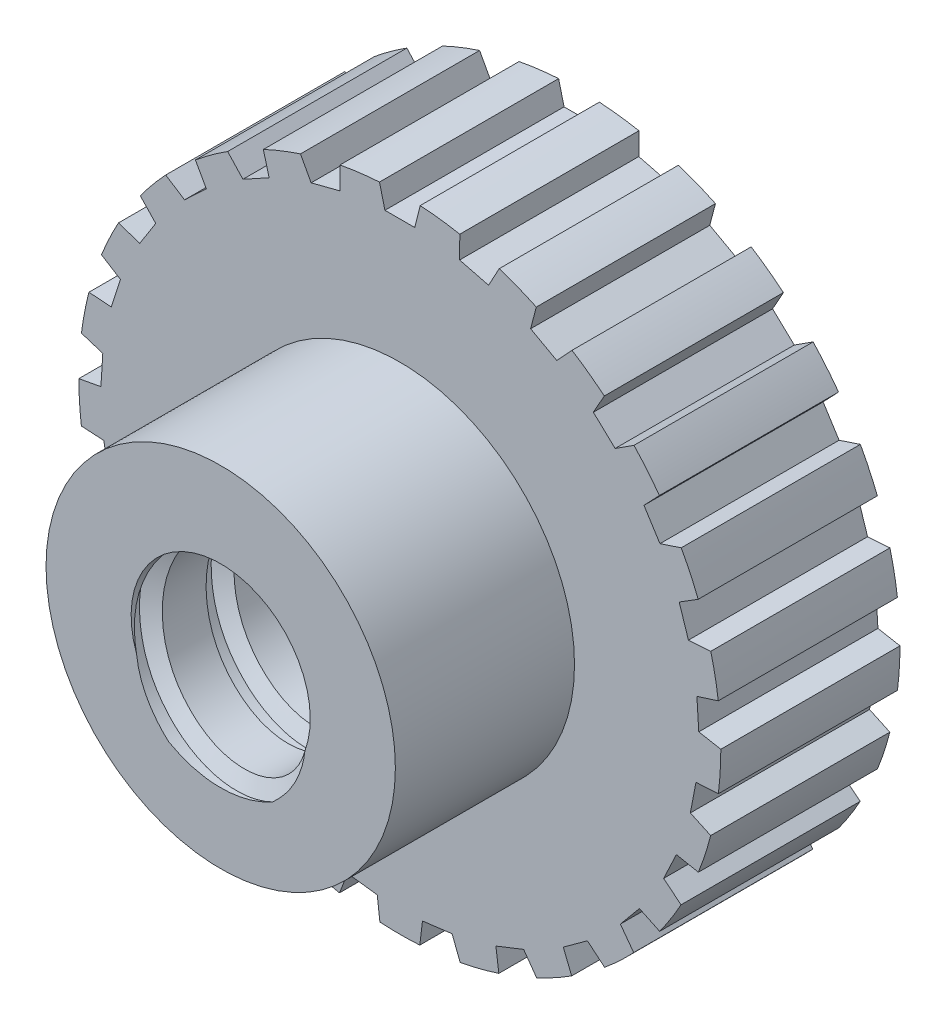
SolidWorks part; units mm, degrees
ref_plane "Front Plane" through (0, 0, 0) normal (0, 0, 1) x (1, 0, 0)
ref_plane "Top Plane" through (0, 0, 0) normal (0, 1, 0) x (1, 0, 0)
ref_plane "Right Plane" through (0, 0, 0) normal (1, 0, 0) x (0, 0, -1)
sketch "Sketch1" plane through (0, 0, 0) normal (0, 0, 1) x (1, 0, 0)
  circle A0 centre (0, 0) radius 5.375
  dimension "D1" = 10.75
extrude "Boss-Extrude2" add sketch "Sketch1" along normal blind 3
sketch "Sketch3" plane through (0, 0, 3) normal (0, 0, 1) x (1, 0, 0)
  circle A0 centre (0, 0) radius 2.925
  dimension "D1" = 5.85
extrude "Boss-Extrude3" add sketch "Sketch3" along normal blind 3
sketch "Sketch4" plane through (0, 0, 6) normal (0, 0, 1) x (1, 0, 0)
  circle A0 centre (0, 0) radius 1.5
  dimension "D1" = 3
extrude "Cut-Extrude1" cut sketch "Sketch4" against normal blind 8
sketch "Sketch5" plane through (0, 0, 3) normal (0, 0, 1) x (1, 0, 0)
  line L0 (0, 0) -> (0, 6.6562) construction
  line L1 (-0.5, 6) -> (0.5, 6)
  line L2 (0.5, 6) -> (0.25, 5)
  line L3 (0.25, 5) -> (-0.25, 5)
  line L4 (-0.25, 5) -> (-0.5, 6)
  line L5 (1.9764, 5.6872) -> (1.4856, 4.7807)
  line L6 (1.0078, 5.9358) -> (1.9764, 5.6872)
  line L7 (1.0013, 4.9051) -> (1.0078, 5.9358)
  line L8 (1.4856, 4.7807) -> (1.0013, 4.9051)
  line L9 (3.3287, 5.017) -> (2.6278, 4.2611)
  line L10 (2.4524, 5.4987) -> (3.3287, 5.017)
  line L11 (2.1897, 4.502) -> (2.4524, 5.4987)
  line L12 (2.6278, 4.2611) -> (2.1897, 4.502)
  line L13 (4.4718, 4.0315) -> (3.605, 3.4737)
  line L14 (3.7428, 4.7161) -> (4.4718, 4.0315)
  line L15 (3.2405, 3.816) -> (3.7428, 4.7161)
  line L16 (3.605, 3.4737) -> (3.2405, 3.816)
  line L17 (5.3339, 2.7928) -> (4.3556, 2.4681)
  line L18 (4.7981, 3.6371) -> (5.3339, 2.7928)
  line L19 (4.0877, 2.8902) -> (4.7981, 3.6371)
  line L20 (4.3556, 2.4681) -> (4.0877, 2.8902)
  line L21 (5.8608, 1.3786) -> (4.8325, 1.3073)
  line L22 (5.5518, 2.3296) -> (5.8608, 1.3786)
  line L23 (4.678, 1.7828) -> (5.5518, 2.3296)
  line L24 (4.8325, 1.3073) -> (4.678, 1.7828)
  line L25 (6.0196, -0.1223) -> (5.0058, 0.0644)
  line L26 (5.9568, 0.8758) -> (6.0196, -0.1223)
  line L27 (4.9744, 0.5635) -> (5.9568, 0.8758)
  line L28 (5.0058, 0.0644) -> (4.9744, 0.5635)
  line L29 (5.8, -1.6154) -> (4.8646, -1.1825)
  line L30 (5.9874, -0.6331) -> (5.8, -1.6154)
  line L31 (4.9583, -0.6913) -> (5.9874, -0.6331)
  line L32 (4.8646, -1.1825) -> (4.9583, -0.6913)
  line L33 (5.2161, -3.0071) -> (4.4177, -2.3551)
  line L34 (5.6419, -2.1023) -> (5.2161, -3.0071)
  line L35 (4.6306, -1.9027) -> (5.6419, -2.1023)
  line L36 (4.4177, -2.3551) -> (4.6306, -1.9027)
  line L37 (4.3044, -4.2098) -> (3.6932, -3.3797)
  line L38 (4.9418, -3.4393) -> (4.3044, -4.2098)
  line L39 (4.0119, -2.9945) -> (4.9418, -3.4393)
  line L40 (3.6932, -3.3797) -> (4.0119, -2.9945)
  line L41 (3.1222, -5.148) -> (2.7367, -4.192)
  line L42 (3.9312, -4.5602) -> (3.1222, -5.148)
  line L43 (3.1412, -3.8981) -> (3.9312, -4.5602)
  line L44 (2.7367, -4.192) -> (3.1412, -3.8981)
  line L45 (1.7439, -5.7627) -> (1.6082, -4.7409)
  line L46 (2.6736, -5.3946) -> (1.7439, -5.7627)
  line L47 (2.0731, -4.5569) -> (2.6736, -5.3946)
  line L48 (1.6082, -4.7409) -> (2.0731, -4.5569)
  line L49 (0.2559, -6.0154) -> (0.3786, -4.9919)
  line L50 (1.2481, -5.89) -> (0.2559, -6.0154)
  line L51 (0.8747, -4.9292) -> (1.2481, -5.89)
  line L52 (0.3786, -4.9919) -> (0.8747, -4.9292)
  line L53 (-1.2481, -5.89) -> (-0.8747, -4.9292)
  line L54 (-0.2559, -6.0154) -> (-1.2481, -5.89)
  line L55 (-0.3786, -4.9919) -> (-0.2559, -6.0154)
  line L56 (-0.8747, -4.9292) -> (-0.3786, -4.9919)
  line L57 (-2.6736, -5.3946) -> (-2.0731, -4.5569)
  line L58 (-1.7439, -5.7627) -> (-2.6736, -5.3946)
  line L59 (-1.6082, -4.7409) -> (-1.7439, -5.7627)
  line L60 (-2.0731, -4.5569) -> (-1.6082, -4.7409)
  line L61 (-3.9312, -4.5602) -> (-3.1412, -3.8981)
  line L62 (-3.1222, -5.148) -> (-3.9312, -4.5602)
  line L63 (-2.7367, -4.192) -> (-3.1222, -5.148)
  line L64 (-3.1412, -3.8981) -> (-2.7367, -4.192)
  line L65 (-4.9418, -3.4393) -> (-4.0119, -2.9945)
  line L66 (-4.3044, -4.2098) -> (-4.9418, -3.4393)
  line L67 (-3.6932, -3.3797) -> (-4.3044, -4.2098)
  line L68 (-4.0119, -2.9945) -> (-3.6932, -3.3797)
  line L69 (-5.6419, -2.1023) -> (-4.6306, -1.9027)
  line L70 (-5.2161, -3.0071) -> (-5.6419, -2.1023)
  line L71 (-4.4177, -2.3551) -> (-5.2161, -3.0071)
  line L72 (-4.6306, -1.9027) -> (-4.4177, -2.3551)
  line L73 (-5.9874, -0.6331) -> (-4.9583, -0.6913)
  line L74 (-5.8, -1.6154) -> (-5.9874, -0.6331)
  line L75 (-4.8646, -1.1825) -> (-5.8, -1.6154)
  line L76 (-4.9583, -0.6913) -> (-4.8646, -1.1825)
  line L77 (-5.9568, 0.8758) -> (-4.9744, 0.5635)
  line L78 (-6.0196, -0.1223) -> (-5.9568, 0.8758)
  line L79 (-5.0058, 0.0644) -> (-6.0196, -0.1223)
  line L80 (-4.9744, 0.5635) -> (-5.0058, 0.0644)
  line L81 (-5.5518, 2.3296) -> (-4.678, 1.7828)
  line L82 (-5.8608, 1.3786) -> (-5.5518, 2.3296)
  line L83 (-4.8325, 1.3073) -> (-5.8608, 1.3786)
  line L84 (-4.678, 1.7828) -> (-4.8325, 1.3073)
  line L85 (-4.7981, 3.6371) -> (-4.0877, 2.8902)
  line L86 (-5.3339, 2.7928) -> (-4.7981, 3.6371)
  line L87 (-4.3556, 2.4681) -> (-5.3339, 2.7928)
  line L88 (-4.0877, 2.8902) -> (-4.3556, 2.4681)
  line L89 (-3.7428, 4.7161) -> (-3.2405, 3.816)
  line L90 (-4.4718, 4.0315) -> (-3.7428, 4.7161)
  line L91 (-3.605, 3.4737) -> (-4.4718, 4.0315)
  line L92 (-3.2405, 3.816) -> (-3.605, 3.4737)
  line L93 (-2.4524, 5.4987) -> (-2.1897, 4.502)
  line L94 (-3.3287, 5.017) -> (-2.4524, 5.4987)
  line L95 (-2.6278, 4.2611) -> (-3.3287, 5.017)
  line L96 (-2.1897, 4.502) -> (-2.6278, 4.2611)
  line L97 (-1.0078, 5.9358) -> (-1.0013, 4.9051)
  line L98 (-1.9764, 5.6872) -> (-1.0078, 5.9358)
  line L99 (-1.4856, 4.7807) -> (-1.9764, 5.6872)
  line L100 (-1.0013, 4.9051) -> (-1.4856, 4.7807)
  point P106 (0, 0)
  dimension "D1" = 1
  dimension "D2" = 5
  dimension "D3" = 0.25
  dimension "D4" = 1
  dimension "D5" = 0.5
  dimension "D6" = 0.5
  dimension "D7" = 25
extrude "Cut-Extrude2" cut sketch "Sketch5" against normal blind 3
sketch "Sketch6" plane through (0, 0, 0) normal (1, 0, 0) x (0, 0, -1)
  line L0 (0, 0) -> (0, -2.7009) construction
  line L1 (0.5, -1) -> (-0.5, -1)
  line L2 (0.5, -1) -> (0.1, -1.75)
  line L3 (0.1, -1.75) -> (-0.1, -1.75)
  line L4 (-0.1, -1.75) -> (-0.5, -1)
  dimension "D1" = 1
  dimension "D2" = 0.2
  dimension "D3" = 0.5
  dimension "D4" = 1
  dimension "D5" = 0.1
  dimension "D6" = 0.75
sketch "Sketch7" plane through (0, 0, 0) normal (0, 0, -1) x (-1, 0, 0)
  circle A0 centre (0, 0) radius 1.5
curve "Helix/Spiral1" pitch 1.2 height 9.6 radius 1.5 centre (0, 0, 0) axis (0, 0, 1) start towards (1, 0, 0)
sweep "Cut-Sweep1" cut profiles "Sketch6" path "Helix/Spiral1" align with end faces yes
